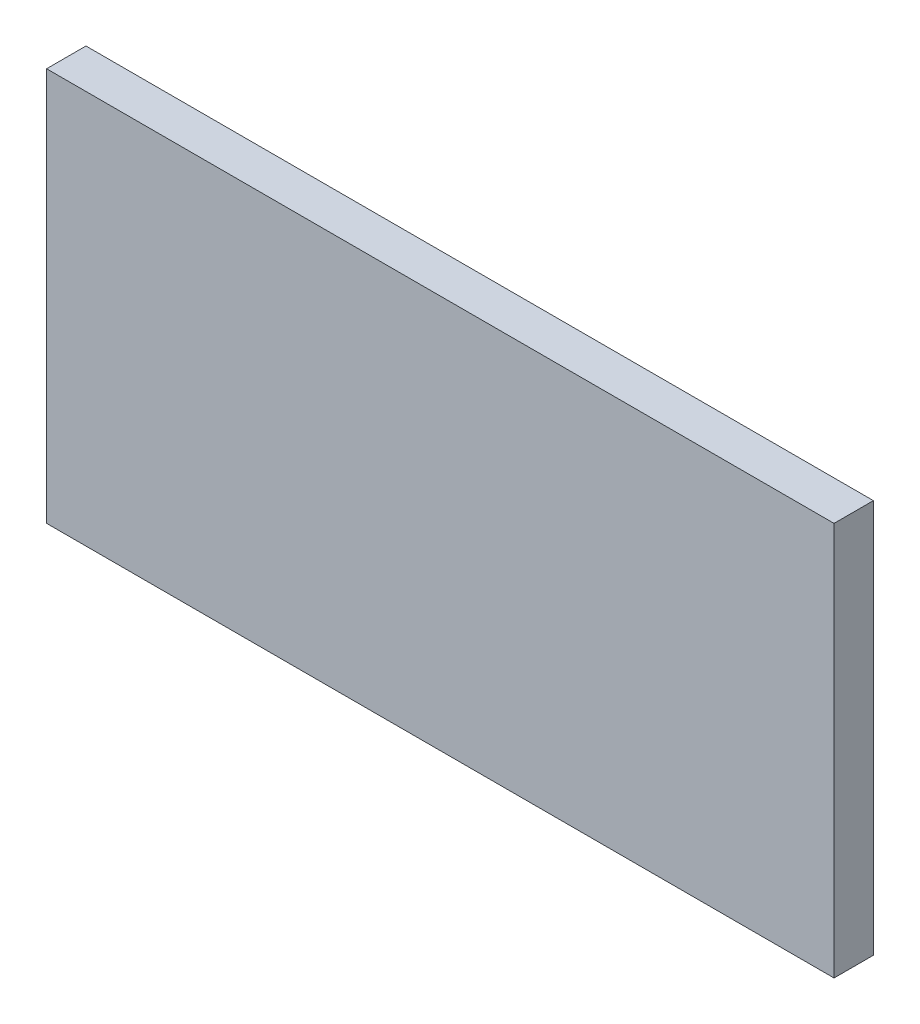
SolidWorks part; units mm, degrees
ref_plane "Front Plane" through (0, 0, 0) normal (0, 0, 1) x (1, 0, 0)
ref_plane "Top Plane" through (0, 0, 0) normal (0, 1, 0) x (1, 0, 0)
ref_plane "Right Plane" through (0, 0, 0) normal (1, 0, 0) x (0, 0, -1)
sketch "Sketch1" plane through (0, 0, 0) normal (0, 0, 1) x (1, 0, 0)
  line L1 (0, 0) -> (-200, 0)
  line L2 (0, 0) -> (0, -100)
  line L3 (0, -100) -> (-200, -100)
  line L4 (-200, 0) -> (-200, -100)
  dimension "D1" = 200
  dimension "D2" = 100
extrude "Boss-Extrude1" add sketch "Sketch1" along normal blind 10
